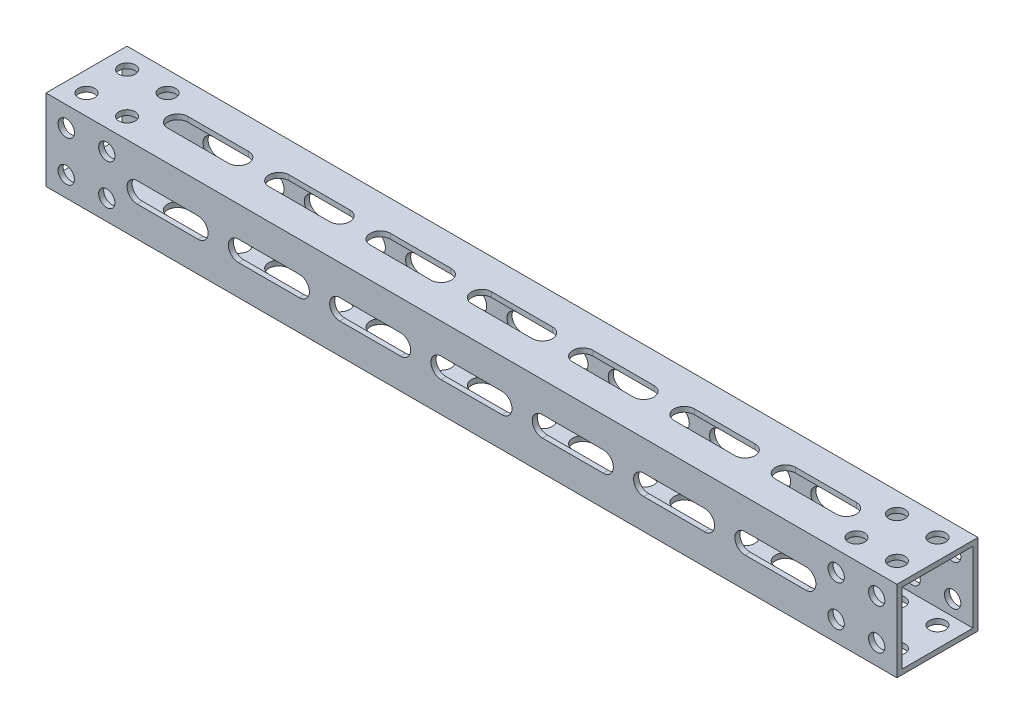
SolidWorks part; units mm, degrees
material "6061-T6 (SS)"
ref_plane "Front" through (0, 0, 0) normal (0, 0, 1) x (1, 0, 0)
ref_plane "Top" through (0, 0, 0) normal (0, 1, 0) x (1, 0, 0)
ref_plane "Right" through (0, 0, 0) normal (1, 0, 0) x (0, 0, -1)
sketch "Sketch1" plane through (0, 0, 0) normal (1, 0, 0) x (0, 0, -1)
  line L1 (12.7, -12.7) -> (-12.7, -12.7)
  line L2 (12.7, -12.7) -> (12.7, 12.7)
  line L3 (12.7, 12.7) -> (-12.7, 12.7)
  line L4 (-12.7, -12.7) -> (-12.7, 12.7)
  line L5 (12.7, -12.7) -> (-12.7, 12.7) construction
  line L6 (12.7, 12.7) -> (-12.7, -12.7) construction
  point P0 (0, 0)
  dimension "D1" = 25.4
extrude "Extrude-Thin1" add sketch "Sketch1" along normal up to surface (266.7 mm away) thin thin type one direction reverse wall 1.5875
sketch "Sketch2" plane through (0, 12.7, 0) normal (0, 1, 0) x (1, 0, 0)
  line L0 (47.625, 0) -> (28.575, 0) construction
  line L1 (47.625, -3.175) -> (28.575, -3.175)
  line L2 (47.625, 3.175) -> (28.575, 3.175)
  line L3 (79.375, 0) -> (60.325, 0) construction
  line L4 (79.375, -3.175) -> (60.325, -3.175)
  line L5 (79.375, 3.175) -> (60.325, 3.175)
  line L6 (111.125, 0) -> (92.075, 0) construction
  line L7 (111.125, -3.175) -> (92.075, -3.175)
  line L8 (111.125, 3.175) -> (92.075, 3.175)
  line L9 (142.875, 0) -> (123.825, 0) construction
  line L10 (142.875, -3.175) -> (123.825, -3.175)
  line L11 (142.875, 3.175) -> (123.825, 3.175)
  line L12 (174.625, 0) -> (155.575, 0) construction
  line L13 (174.625, -3.175) -> (155.575, -3.175)
  line L14 (174.625, 3.175) -> (155.575, 3.175)
  line L15 (206.375, 0) -> (187.325, 0) construction
  line L16 (206.375, -3.175) -> (187.325, -3.175)
  line L17 (206.375, 3.175) -> (187.325, 3.175)
  line L18 (0, 12.7) -> (0, -12.7) construction
  line L19 (238.125, 0) -> (219.075, 0) construction
  line L20 (238.125, -3.175) -> (219.075, -3.175)
  line L21 (238.125, 3.175) -> (219.075, 3.175)
  line L22 (266.7, -12.7) -> (266.7, 12.7) construction
  arc A0 (47.625, -3.175) -> (47.625, 3.175) centre (47.625, 0) ccw
  arc A1 (28.575, 3.175) -> (28.575, -3.175) centre (28.575, 0) ccw
  arc A2 (79.375, -3.175) -> (79.375, 3.175) centre (79.375, 0) ccw
  arc A3 (60.325, 3.175) -> (60.325, -3.175) centre (60.325, 0) ccw
  arc A4 (111.125, -3.175) -> (111.125, 3.175) centre (111.125, 0) ccw
  arc A5 (92.075, 3.175) -> (92.075, -3.175) centre (92.075, 0) ccw
  arc A6 (142.875, -3.175) -> (142.875, 3.175) centre (142.875, 0) ccw
  arc A7 (123.825, 3.175) -> (123.825, -3.175) centre (123.825, 0) ccw
  arc A8 (174.625, -3.175) -> (174.625, 3.175) centre (174.625, 0) ccw
  arc A9 (155.575, 3.175) -> (155.575, -3.175) centre (155.575, 0) ccw
  arc A10 (206.375, -3.175) -> (206.375, 3.175) centre (206.375, 0) ccw
  arc A11 (187.325, 3.175) -> (187.325, -3.175) centre (187.325, 0) ccw
  arc A12 (238.125, -3.175) -> (238.125, 3.175) centre (238.125, 0) ccw
  arc A13 (219.075, 3.175) -> (219.075, -3.175) centre (219.075, 0) ccw
  point P3 (38.1, 0)
  point P10 (69.85, 0)
  point P18 (101.6, 0)
  point P25 (133.35, 0)
  point P32 (165.1, 0)
  point P39 (196.85, 0)
  point P48 (228.6, 0)
  dimension "D1" = 6.35
  dimension "D2" = 19.05
  dimension "D4" = 28.575
  dimension "D5" = 31.75
  dimension "D6" = 28.575
  dimension "D3" = 7
extrude "Cut-Extrude1" cut sketch "Sketch2" against normal through all
sketch "Sketch3" plane through (0, 0, -12.7) normal (0, 0, -1) x (-1, 0, 0)
  line L0 (-28.575, 0) -> (-47.625, 0) construction
  line L1 (-28.575, -3.175) -> (-47.625, -3.175)
  line L2 (-28.575, 3.175) -> (-47.625, 3.175)
  line L3 (0, -12.7) -> (0, 12.7) construction
  line L4 (-60.325, 0) -> (-79.375, 0) construction
  line L5 (-60.325, -3.175) -> (-79.375, -3.175)
  line L6 (-60.325, 3.175) -> (-79.375, 3.175)
  line L7 (-92.075, 0) -> (-111.125, 0) construction
  line L8 (-92.075, -3.175) -> (-111.125, -3.175)
  line L9 (-92.075, 3.175) -> (-111.125, 3.175)
  line L10 (-123.825, 0) -> (-142.875, 0) construction
  line L11 (-123.825, -3.175) -> (-142.875, -3.175)
  line L12 (-123.825, 3.175) -> (-142.875, 3.175)
  line L13 (-155.575, 0) -> (-174.625, 0) construction
  line L14 (-155.575, -3.175) -> (-174.625, -3.175)
  line L15 (-155.575, 3.175) -> (-174.625, 3.175)
  line L16 (-187.325, 0) -> (-206.375, 0) construction
  line L17 (-187.325, -3.175) -> (-206.375, -3.175)
  line L18 (-187.325, 3.175) -> (-206.375, 3.175)
  line L19 (-219.075, 0) -> (-238.125, 0) construction
  line L20 (-219.075, -3.175) -> (-238.125, -3.175)
  line L21 (-219.075, 3.175) -> (-238.125, 3.175)
  line L22 (-28.575, 0) -> (-60.325, 0) construction
  arc A0 (-28.575, -3.175) -> (-28.575, 3.175) centre (-28.575, 0) ccw
  arc A1 (-47.625, 3.175) -> (-47.625, -3.175) centre (-47.625, 0) ccw
  arc A2 (-60.325, -3.175) -> (-60.325, 3.175) centre (-60.325, 0) ccw
  arc A3 (-79.375, 3.175) -> (-79.375, -3.175) centre (-79.375, 0) ccw
  arc A4 (-92.075, -3.175) -> (-92.075, 3.175) centre (-92.075, 0) ccw
  arc A5 (-111.125, 3.175) -> (-111.125, -3.175) centre (-111.125, 0) ccw
  arc A6 (-123.825, -3.175) -> (-123.825, 3.175) centre (-123.825, 0) ccw
  arc A7 (-142.875, 3.175) -> (-142.875, -3.175) centre (-142.875, 0) ccw
  arc A8 (-155.575, -3.175) -> (-155.575, 3.175) centre (-155.575, 0) ccw
  arc A9 (-174.625, 3.175) -> (-174.625, -3.175) centre (-174.625, 0) ccw
  arc A10 (-187.325, -3.175) -> (-187.325, 3.175) centre (-187.325, 0) ccw
  arc A11 (-206.375, 3.175) -> (-206.375, -3.175) centre (-206.375, 0) ccw
  arc A12 (-219.075, -3.175) -> (-219.075, 3.175) centre (-219.075, 0) ccw
  arc A13 (-238.125, 3.175) -> (-238.125, -3.175) centre (-238.125, 0) ccw
  point P3 (-38.1, 0)
  point P13 (-69.85, 0)
  point P20 (-101.6, 0)
  point P27 (-133.35, 0)
  point P34 (-165.1, 0)
  point P41 (-196.85, 0)
  point P48 (-228.6, 0)
  dimension "D2" = 19.05
  dimension "D3" = 28.575
  dimension "D1" = 6.35
  dimension "D5" = 31.75
  dimension "D4" = 7
extrude "Cut-Extrude2" cut sketch "Sketch3" against normal through all
sketch "Sketch6" plane through (0, 0, 12.7) normal (0, 0, 1) x (1, 0, 0)
  line L0 (0, 0) -> (12.1609, 0) construction
  line L1 (0, 12.7) -> (0, -12.7) construction
  line L3 (266.7, 12.7) -> (0, 12.7) construction
  line L4 (133.35, -12.7) -> (133.35, 36.0977) construction
  line L5 (266.7, -12.7) -> (0, -12.7) construction
  point P0 (6.35, 6.35)
  point P2 (19.05, 6.35)
  point P11 (19.05, -6.35)
  point P12 (6.35, -6.35)
  point P21 (260.35, -6.35)
  point P22 (247.65, -6.35)
  point P23 (247.65, 6.35)
  point P24 (260.35, 6.35)
  dimension "D1" = 6.35
  dimension "D2" = 6.35
  dimension "D3" = 12.7
hole_wizard "#10 Clearance Hole1" positions "Sketch6" profile "Sketch5" hole size "#10" standard "ANSI Inch" end condition through all
sketch "Sketch5" plane through (6.35, 6.35, 12.7) normal (1, 0, 0) x (0, -1, 0)
  line L0 (0, 0) -> (0, 25.4)
  line L1 (0, 25.4) -> (2.5527, 25.4)
  line L2 (2.5527, 25.4) -> (2.5527, 0)
  line L5 (2.5527, 0) -> (0, 0)
  line L11 (0, -6.35) -> (0, 107.95) construction
  dimension "Thru Hole Dia." = 5.1054
  dimension "Thru Hole Depth" = 25.4
sketch "Sketch9" plane through (0, 12.7, 0) normal (0, 1, 0) x (1, 0, 0)
  line L0 (0, 0) -> (13.3717, 0) construction
  line L1 (0, 12.7) -> (0, -12.7) construction
  line L4 (133.35, -12.7) -> (133.35, 19.8462) construction
  line L5 (266.7, -12.7) -> (0, -12.7) construction
  line L7 (266.7, 12.7) -> (0, 12.7) construction
  point P0 (6.35, 6.35)
  point P2 (19.05, 6.35)
  point P20 (19.05, -6.35)
  point P21 (6.35, -6.35)
  point P22 (260.35, -6.35)
  point P23 (247.65, -6.35)
  point P24 (247.65, 6.35)
  point P25 (260.35, 6.35)
  dimension "D1" = 6.35
  dimension "D2" = 6.35
  dimension "D3" = 12.7
hole_wizard "#10 Clearance Hole2" positions "Sketch9" profile "Sketch8" hole size "#10" standard "ANSI Inch" end condition through all
sketch "Sketch8" plane through (6.35, 12.7, -6.35) normal (1, 0, 0) x (0, 0, 1)
  line L0 (0, 0) -> (0, 25.4)
  line L1 (0, 25.4) -> (2.5527, 25.4)
  line L2 (2.5527, 25.4) -> (2.5527, 0)
  line L5 (2.5527, 0) -> (0, 0)
  line L11 (0, -6.35) -> (0, 107.95) construction
  dimension "Thru Hole Dia." = 5.1054
  dimension "Thru Hole Depth" = 25.4
